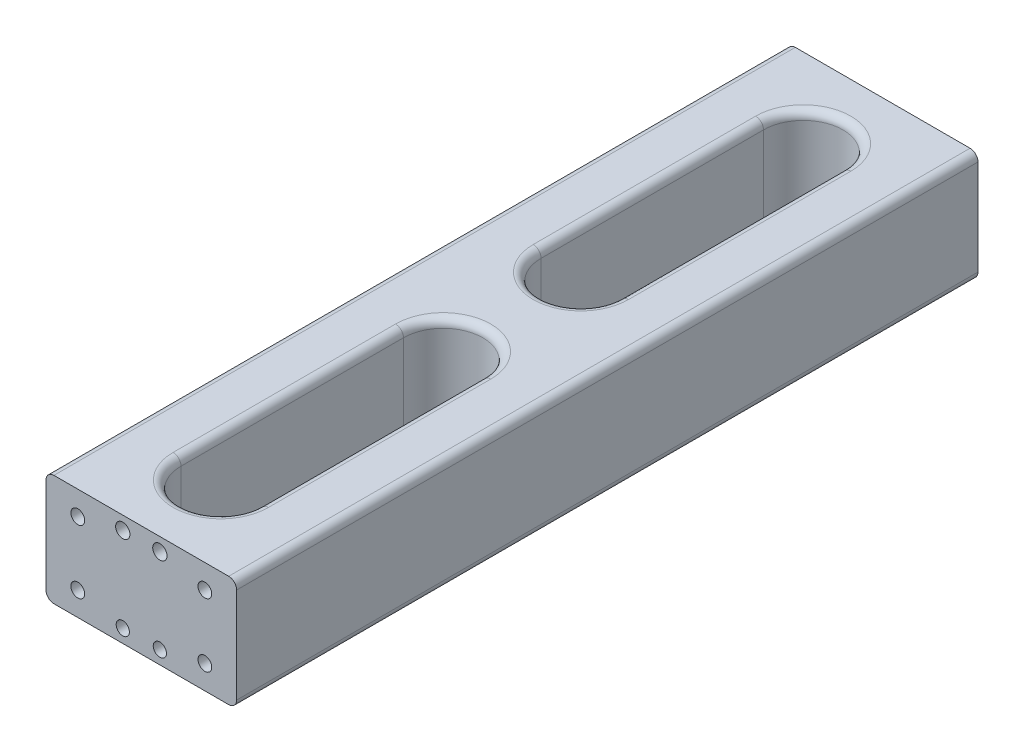
SolidWorks part; units mm, degrees
ref_plane "정면" through (0, 0, 0) normal (0, 0, 1) x (1, 0, 0)
ref_plane "윗면" through (0, 0, 0) normal (0, 1, 0) x (1, 0, 0)
ref_plane "우측면" through (0, 0, 0) normal (1, 0, 0) x (0, 0, -1)
sketch "스케치1" plane through (0, 0, 0) normal (0, 0, 1) x (1, 0, 0)
  line L0 (0, 10.5) -> (0, -10.5) construction
  line L1 (18, -10.5) -> (-18, -10.5)
  line L2 (18, -10.5) -> (18, 10.5)
  line L3 (18, 10.5) -> (-18, 10.5)
  line L4 (-18, -10.5) -> (-18, 10.5)
  line L5 (18, -10.5) -> (-18, 10.5) construction
  line L6 (18, 10.5) -> (-18, -10.5) construction
  line L7 (18, 0) -> (-18, 0) construction
  circle A0 centre (12, 6) radius 1.3
  circle A1 centre (-12, 6) radius 1.3
  circle A2 centre (12, -6) radius 1.3
  circle A3 centre (-12, -6) radius 1.3
  circle A4 centre (3.5, -8) radius 1.25
  circle A5 centre (-3.5, -8) radius 1.25
  circle A6 centre (3.5, 8) radius 1.35
  circle A7 centre (-3.5, 8) radius 1.35
  point P1 (0, 0)
extrude "보스-돌출1" add sketch "스케치1" along normal blind 140 contours A0 | A6 | A7 | A1 | A3 | A5 | A4 | A2 | L4 L1 L2 L3 A5 A4 A1 A0 A2 A3 A6 A7 region at (0, -0.0183, 0) region at (12, 6, 0) region at (-12, 6, 0) region at (12, -6, 0) region at (-12, -6, 0) region at (3.5, -8, 0) region at (-3.5, -8, 0) region at (3.5, 8, 0) region at (-3.5, 8, 0)
extrude "컷-돌출1" cut sketch "스케치1<5>" along normal blind 4 contours A0 | A6 | A7 | A1 | A3 | A5 | A4 | A2 region at (12, 6, 0) region at (-12, 6, 0) region at (-12, -6, 0) region at (3.5, 8, 0) region at (-3.5, 8, 0)
sketch "스케치1<5>" plane through (0, 0, 0) normal (0, 0, 1) x (1, 0, 0) same geometry as "스케치1"
extrude "컷-돌출2" cut sketch "스케치1<6>" against normal blind 4 from surface contours A6 | A0 | A7 | A1 | A3 | A5 | A4 | A2 region at (12, 6, 0) region at (-12, 6, 0) region at (12, -6, 0) region at (-12, -6, 0) region at (3.5, -8, 0) region at (-3.5, -8, 0) region at (3.5, 8, 0) region at (-3.5, 8, 0) starting at face at (0, 0, 140)
sketch "스케치1<6>" plane through (0, 0, 0) normal (0, 0, 1) x (1, 0, 0) same geometry as "스케치1"
sketch "스케치2" plane through (0, 10.5, 0) normal (0, 1, 0) x (1, 0, 0)
  line L0 (18, -70) -> (-18, -70) construction
  line L1 (18, -140) -> (18, 0) construction
  line L2 (-18, -140) -> (-18, 0) construction
  line L3 (0, -15) -> (0, -57) construction
  line L4 (7.5, -15) -> (7.5, -57)
  line L5 (-7.5, -15) -> (-7.5, -57)
  line L6 (0, -125) -> (0, -83) construction
  line L7 (7.5, -125) -> (7.5, -83)
  line L8 (-7.5, -125) -> (-7.5, -83)
  line L9 (18, 0) -> (-18, 0) construction
  arc A0 (7.5, -15) -> (-7.5, -15) centre (0, -15) ccw
  arc A1 (-7.5, -57) -> (7.5, -57) centre (0, -57) ccw
  arc A2 (7.5, -125) -> (-7.5, -125) centre (0, -125) cw
  arc A3 (-7.5, -83) -> (7.5, -83) centre (0, -83) cw
  point P9 (0, -36)
  point P17 (0, -104)
  dimension "D1" = 42
  dimension "D2" = 15
  dimension "D3" = 15
extrude "컷-돌출3" cut sketch "스케치2" against normal up to next
fillet "필렛1" radius 1.5 20 edges at (0, 10.5, 132.5) (-7.5, 10.5, 104) (0, 10.5, 75.5) (0, 10.5, 64.5) (-7.5, 10.5, 36) (0, 10.5, 7.5) (0, -10.5, 7.5) (7.5, -10.5, 36) (0, -10.5, 64.5) (0, -10.5, 75.5) (7.5, -10.5, 104) (0, -10.5, 132.5) (7.5, 10.5, 104) (7.5, 10.5, 36) (-7.5, -10.5, 36) (-7.5, -10.5, 104) (-18, 10.5, 70) (-18, -10.5, 70) (18, -10.5, 70) (18, 10.5, 70)
